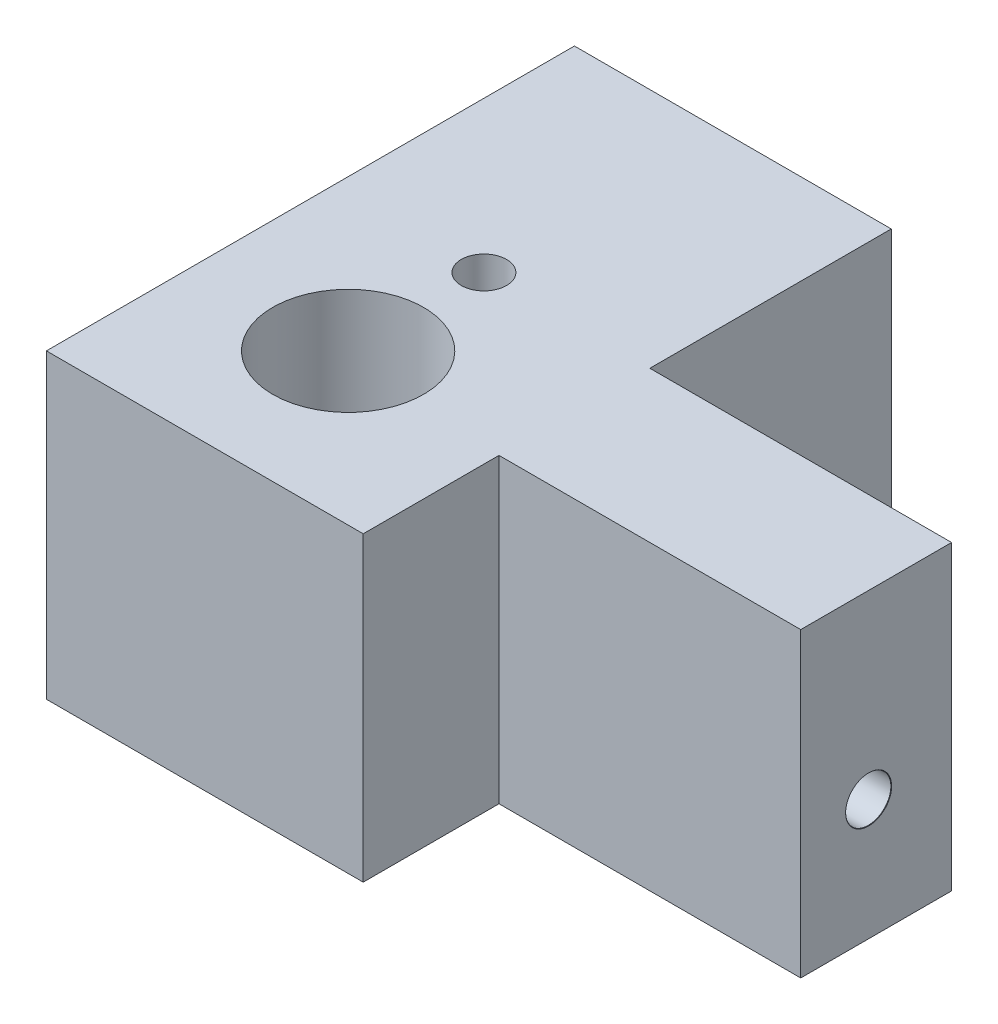
SolidWorks part; units mm, degrees
ref_plane "Front Plane" through (0, 0, 0) normal (0, 0, 1) x (1, 0, 0)
ref_plane "Top Plane" through (0, 0, 0) normal (0, 1, 0) x (1, 0, 0)
ref_plane "Right Plane" through (0, 0, 0) normal (1, 0, 0) x (0, 0, -1)
sketch "Sketch1" plane through (0, 0, 0) normal (0, 1, 0) x (1, 0, 0)
  line L1 (-10.5256, 22.3096) -> (38.4744, 22.3096)
  line L2 (-10.5256, 22.3096) -> (-10.5256, -12.6904)
  line L3 (-10.5256, -12.6904) -> (38.4744, -12.6904)
  line L4 (38.4744, 22.3096) -> (38.4744, -12.6904)
  dimension "D1" = 35
  dimension "D2" = 49
extrude "Boss-Extrude1" add sketch "Sketch1" along normal blind 20
hole_wizard "Ø3.0mm Dowel Hole1" positions "Sketch3" profile "Sketch4" hole size "Ø3.0" standard "ANSI Metric"
sketch "Sketch3" plane through (0, 0, -22.3096) normal (0, 0, -1) x (-1, 0, 0)
  line L0 (-38.4744, 20) -> (-38.4744, 0) construction
  line L3 (-38.4744, 0) -> (10.5256, 0) construction
  point P0 (-7.4744, 16)
  dimension "D1" = 31
  dimension "D2" = 16
sketch "Sketch4" plane through (7.4744, 16, -22.3096) normal (1, 0, 0) x (0, 1, 0)
  line L0 (0, 0) -> (0, 12)
  line L1 (0, 12) -> (1.5, 11.0987)
  line L2 (1.5, 11.0987) -> (1.5, 0.025)
  line L3 (1.5, 0.025) -> (1.525, 0)
  line L5 (1.525, 0) -> (0, 0)
  line L6 (-1.5, 0.025) -> (-1.525, 0) construction
  line L10 (0, 12) -> (-1.5, 11.0987) construction
  line L11 (0, -6.35) -> (0, 107.95) construction
  dimension "Hole Dia." = 3
  dimension "Hole Depth" = 12
  dimension "Near C'Sink Dia." = 3.05
  dimension "Near C'Sink Angle" = 90
  dimension "Drill Angle" = 118
hole_wizard "Ø3.0mm Dowel Hole2" positions "Sketch7" profile "Sketch8" hole size "Ø3.0" standard "ANSI Metric"
sketch "Sketch7" plane through (38.4744, 0, 0) normal (1, 0, 0) x (0, 0, -1)
  line L0 (-12.6904, 0) -> (22.3096, 0) construction
  line L1 (22.3096, 20) -> (22.3096, 0) construction
  point P0 (0.8096, 8)
  dimension "D1" = 8
  dimension "D2" = 21.5
sketch "Sketch8" plane through (38.4744, 8, -0.8096) normal (0, 1, 0) x (0, 0, -1)
  line L0 (0, 0) -> (0, 12.9013)
  line L1 (0, 12.9013) -> (1.5, 12)
  line L2 (1.5, 12) -> (1.5, 0.025)
  line L3 (1.5, 0.025) -> (1.525, 0)
  line L5 (1.525, 0) -> (0, 0)
  line L6 (-1.5, 0.025) -> (-1.525, 0) construction
  line L10 (0, 12.9013) -> (-1.5, 12) construction
  line L11 (0, -6.35) -> (0, 107.95) construction
  dimension "Hole Dia." = 3
  dimension "Hole Depth" = 12
  dimension "Near C'Sink Dia." = 3.05
  dimension "Near C'Sink Angle" = 90
  dimension "Drill Angle" = 118
hole_wizard "Ø3.0mm Dowel Hole3" positions "Sketch9" profile "Sketch10" hole size "Ø3.0" standard "ANSI Metric" end condition through all
sketch "Sketch9" plane through (0, 0, 0) normal (0, -1, 0) x (-1, 0, 0)
  line L1 (-38.4744, 22.3096) -> (10.5256, 22.3096) construction
  line L3 (-38.4744, -12.6904) -> (-38.4744, 22.3096) construction
  point P0 (-7.4744, 6.3096)
  dimension "D1" = 31
  dimension "D2" = 16
sketch "Sketch10" plane through (7.4744, 0, -6.3096) normal (1, 0, 0) x (0, 0, -1)
  line L0 (0, 0) -> (0, 20)
  line L1 (0, 20) -> (1.5, 20)
  line L2 (1.5, 20) -> (1.5, 0.025)
  line L3 (1.5, 0.025) -> (1.525, 0)
  line L5 (1.525, 0) -> (0, 0)
  line L6 (-1.5, 0.025) -> (-1.525, 0) construction
  line L11 (0, -6.35) -> (0, 107.95) construction
  dimension "Thru Hole Dia." = 3
  dimension "Thru Hole Depth" = 20
  dimension "Near C'Sink Dia." = 3.05
  dimension "Near C'Sink Angle" = 90
sketch "Sketch14" plane through (0, 20, 0) normal (0, 1, 0) x (1, 0, 0)
  line L0 (-10.5256, -12.6904) -> (38.4744, -12.6904) construction
  line L1 (-10.5256, 22.3096) -> (-2.5256, 22.3096)
  line L2 (-10.5256, 22.3096) -> (-10.5256, -12.6904)
  line L3 (-10.5256, -12.6904) -> (-2.5256, -12.6904)
  line L4 (-2.5256, 22.3096) -> (-2.5256, -12.6904)
  line L7 (18.4744, 22.3096) -> (38.4744, 22.3096)
  line L8 (18.4744, 22.3096) -> (18.4744, 6.3096)
  line L9 (18.4744, 6.3096) -> (38.4744, 6.3096)
  line L10 (38.4744, 22.3096) -> (38.4744, 6.3096)
  line L13 (38.4744, -12.6904) -> (18.4744, -12.6904)
  line L14 (38.4744, -12.6904) -> (38.4744, -3.6904)
  line L15 (38.4744, -3.6904) -> (18.4744, -3.6904)
  line L16 (18.4744, -12.6904) -> (18.4744, -3.6904)
  dimension "D1" = 0
  dimension "D2" = 8
  dimension "D3" = 9
  dimension "D4" = 20
  dimension "D5" = 10
  dimension "D6" = 20
extrude "Cut-Extrude3" cut sketch "Sketch14" against normal blind 28
sketch "Sketch15" plane through (0, 20, 0) normal (0, 1, 0) x (1, 0, 0)
  line L0 (18.4744, 22.3096) -> (-2.5256, 22.3096) construction
  circle A0 centre (7.4744, -2.6904) radius 5
  dimension "D1" = 25
extrude "Cut-Extrude4" cut sketch "Sketch15" against normal blind 30
